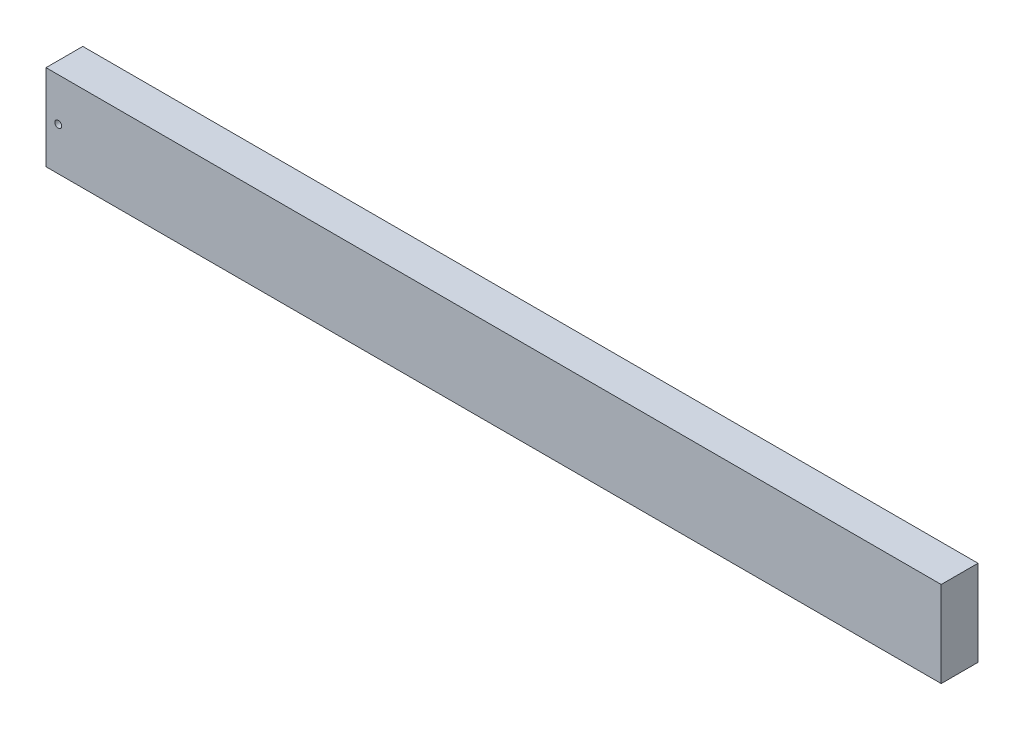
SolidWorks part; units mm, degrees
ref_plane "Front Plane" through (0, 0, 0) normal (0, 0, 1) x (1, 0, 0)
ref_plane "Top Plane" through (0, 0, 0) normal (0, 1, 0) x (1, 0, 0)
ref_plane "Right Plane" through (0, 0, 0) normal (1, 0, 0) x (0, 0, -1)
sketch "Sketch1" plane through (0, 0, 0) normal (1, 0, 0) x (0, 0, -1)
  line L1 (-19.05, -44.45) -> (19.05, -44.45)
  line L2 (-19.05, -44.45) -> (-19.05, 44.45)
  line L3 (-19.05, 44.45) -> (19.05, 44.45)
  line L4 (19.05, -44.45) -> (19.05, 44.45)
  line L5 (-19.05, -44.45) -> (19.05, 44.45) construction
  line L6 (-19.05, 44.45) -> (19.05, -44.45) construction
  point P0 (0, 0)
  dimension "D1" = 88.9
  dimension "D2" = 38.1
extrude "Boss-Extrude1" add sketch "Sketch1" along normal blind 927.1
hole_wizard "9/32 (0.28125) Diameter Hole1" positions "Sketch3" profile "Sketch2" hole size "9/32" standard "ANSI Inch" end condition through all
sketch "Sketch3" plane through (0, 0, 19.05) normal (0, 0, 1) x (1, 0, 0)
  line L1 (927.1, -44.45) -> (0, -44.45) construction
  line L2 (927.1, 44.45) -> (927.1, -44.45) construction
  point P0 (12.7, 0)
  dimension "D1" = 914.4
  dimension "D2" = 44.45
sketch "Sketch2" plane through (12.7, 0, 19.05) normal (1, 0, 0) x (0, -1, 0)
  line L0 (0, 0) -> (0, 38.1)
  line L1 (0, 38.1) -> (3.5719, 38.1)
  line L2 (3.5719, 38.1) -> (3.5719, 0)
  line L5 (3.5719, 0) -> (0, 0)
  line L11 (0, -6.35) -> (0, 107.95) construction
  dimension "Thru Hole Dia." = 7.1437
  dimension "Thru Hole Depth" = 38.1
